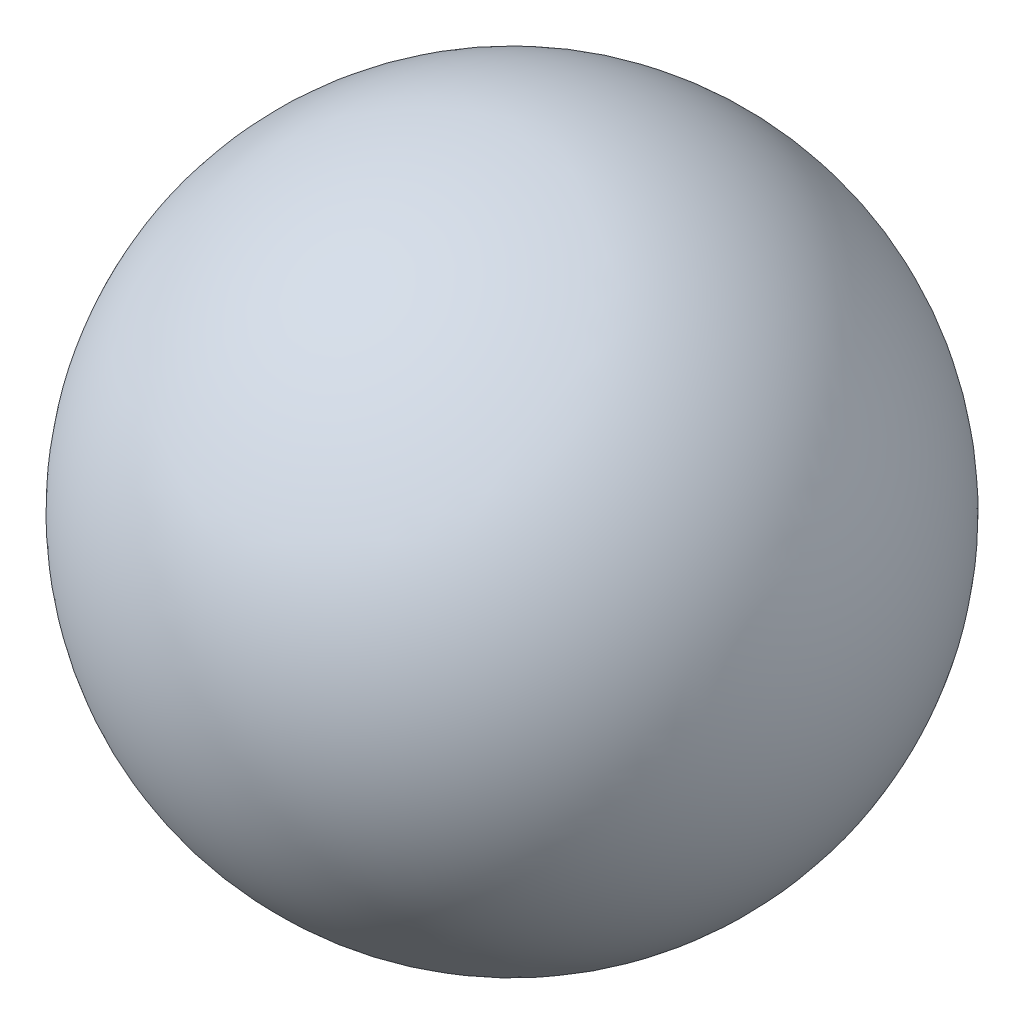
SolidWorks part; units mm, degrees
ref_plane "Front" through (0, 0, 0) normal (0, 0, 1) x (1, 0, 0)
ref_plane "Top" through (0, 0, 0) normal (0, 1, 0) x (1, 0, 0)
ref_plane "Right" through (0, 0, 0) normal (1, 0, 0) x (0, 0, -1)
ref_axis "side-side" through (80.9, 0, 0) along (-1, 0, 0)
ref_axis "up-down" through (0, 50, 0) along (0, -1, 0)
ref_axis "front-back" through (0, 0, -80.9) along (0, 0, 1)
sketch "Sketch1" plane through (0, 0, 0) normal (0, 1, 0) x (1, 0, 0)
  line L0 (-47.625, 0) -> (47.625, 0)
  line L1 (47.625, 0) -> (82.8157, 0) construction
  arc A0 (-47.625, 0) -> (47.625, 0) centre (0, 0) ccw
  dimension "D1" = 95.25
revolve "Revolve1" add sketch "Sketch1" angle 360 about L1
